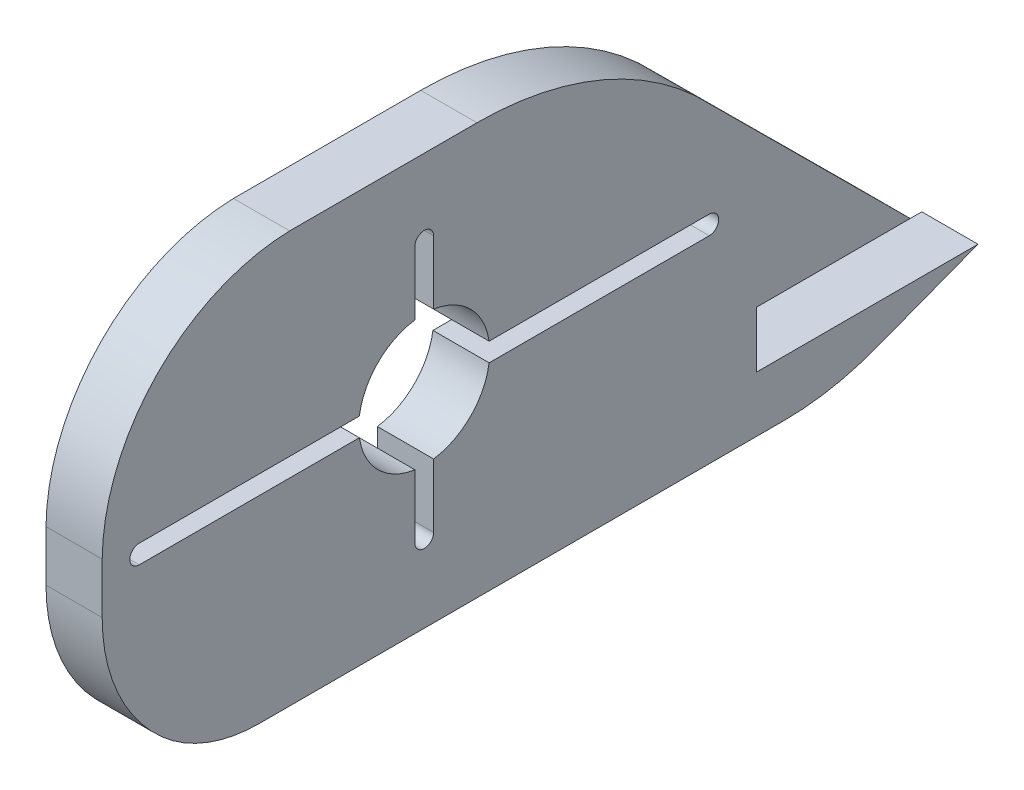
SolidWorks part; units mm, degrees
ref_plane "Front Plane" through (0, 0, 0) normal (0, 0, 1) x (1, 0, 0)
ref_plane "Top Plane" through (0, 0, 0) normal (0, 1, 0) x (1, 0, 0)
ref_plane "Right Plane" through (0, 0, 0) normal (1, 0, 0) x (0, 0, -1)
sketch "Sketch1" plane through (0, 0, 0) normal (0, 1, 0) x (1, 0, 0)
  line L8 (-9.9025, 36.4566) -> (-20.3157, 23.2959) construction
  line L10 (0, 0) -> (0, -15.9475) construction
  line L12 (-9.9025, 36.4566) -> (-20.3157, 23.2959)
  line L15 (-20.9631, 21.4344) -> (-20.9631, -5.9026) construction
  line L16 (-19.4729, -6.2109) -> (-9.8452, -11.8182)
  line L19 (-9.8452, -11.8182) -> (-9.8452, -21.8182)
  line L22 (-9.8452, -21.8182) -> (-6.8452, -21.8182)
  line L23 (-6.8452, -21.8182) -> (-6.8452, -12.4305)
  line L24 (-6.8452, -12.4305) -> (6.8452, -12.4305)
  line L25 (-4.1595, 37.5951) -> (-7.5499, 37.5951)
  line L26 (4.1595, 37.5951) -> (1.3957, 42.8144)
  line L27 (1.3957, 42.8144) -> (0, 43.4367)
  line L28 (24.762, -2.7815) -> (19.4729, -6.2109)
  line L29 (26.1299, 14.9044) -> (26.1299, -0.2643)
  line L30 (18.8536, 25.1438) -> (25.4825, 16.7659)
  line L31 (-18.8536, 25.1438) -> (-25.4825, 16.7659)
  line L32 (-26.1299, 14.9044) -> (-26.1299, -0.2643)
  line L33 (-24.762, -2.7815) -> (-19.4729, -6.2109)
  line L34 (4.1595, 37.5951) -> (7.5499, 37.5951)
  line L35 (6.8452, -21.8182) -> (6.8452, -12.4305)
  line L36 (9.8452, -21.8182) -> (6.8452, -21.8182)
  line L37 (9.8452, -11.8182) -> (9.8452, -21.8182)
  line L38 (19.4729, -6.2109) -> (9.8452, -11.8182)
  line L39 (0, 0) -> (0, 47.8638) construction
  line L40 (-1.3957, 42.8144) -> (0, 43.4367)
  line L41 (-4.1595, 37.5951) -> (-1.3957, 42.8144)
  line L42 (9.9025, 36.4566) -> (20.3157, 23.2959)
  arc A1 (-7.5499, 37.5951) -> (-9.9025, 36.4566) centre (-7.5499, 34.5951) ccw construction
  circle A4 centre (-5.0017, 34.5359) radius 1.5 construction
  circle A8 centre (-5.0017, 34.5359) radius 1.5
  arc A11 (-7.5499, 37.5951) -> (-9.9025, 36.4566) centre (-7.5499, 34.5951) ccw
  arc A12 (-19.7137, -6.0547) -> (-19.4729, -6.2109) centre (-17.9631, -3.6185) ccw
  arc A14 (25.4825, 16.7659) -> (26.1299, 14.9044) centre (23.1299, 14.9044) cw
  arc A15 (26.1299, -0.2643) -> (24.762, -2.7815) centre (23.1299, -0.2643) cw
  arc A16 (19.7137, -6.0547) -> (19.4729, -6.2109) centre (17.9631, -3.6185) cw
  arc A17 (-26.1299, -0.2643) -> (-24.762, -2.7815) centre (-23.1299, -0.2643) ccw
  arc A18 (-25.4825, 16.7659) -> (-26.1299, 14.9044) centre (-23.1299, 14.9044) ccw
  arc A19 (7.5499, 37.5951) -> (9.9025, 36.4566) centre (7.5499, 34.5951) cw
  circle A20 centre (5.0017, 34.5359) radius 1.5
  point P28 (0.1548, -12.4305)
  point P33 (-20.9631, -5.343)
  point P37 (0, -12.4305)
  point P41 (0.1548, -12.4305)
  point P46 (26.1299, 15.9477)
  point P48 (26.1299, -1.8946)
  point P49 (-0.1548, -12.4305)
  point P50 (20.9631, -5.343)
  point P54 (-26.1299, -1.8946)
  point P57 (-26.1299, 15.9477)
  dimension "D1" = 3
  dimension "D3" = 3
  dimension "D4" = 10
extrude "Boss-Extrude2" add sketch "Sketch1" along normal blind 3 contours A11 L12 A12 L16 L19 L22 L23 A8 region at (0, 0, -10.7329)
mirror "Mirror1" about plane through (0, 0, 0) normal (1, 0, 0) of "Boss-Extrude2"
sketch "Sketch3" plane through (9.8452, 0, 0) normal (1, 0, 0) x (0, 0, -1)
  line L0 (0, 0) -> (-5.4214, -2.0662)
  line L1 (-10.362, -2.9757) -> (-38.362, -2.9757)
  line L2 (-46.7647, 6.1171) -> (-46.7647, 8.8248)
  line L3 (-36.7549, 18.9944) -> (-26.7549, 18.9944)
  line L4 (-14.3131, 13.6377) -> (-3.6185, 3)
  line L5 (-3.6185, 3) -> (0, 0)
  line L6 (-11.8182, 3) -> (-11.8182, 0) construction
  arc A0 (-5.4214, -2.0662) -> (-10.362, -2.9757) centre (-10.362, 10.8976) cw
  arc A1 (-38.362, -2.9757) -> (-43.5481, -1.0139) centre (-38.362, 4.8597) cw
  arc A2 (-43.5481, -1.0139) -> (-46.7647, 6.1171) centre (-37.2518, 6.1171) cw
  circle A5 centre (-29.5682, 8.0684) radius 5 construction
  arc A7 (-26.7549, 18.9944) -> (-14.3131, 13.6377) centre (-26.7549, 1.8671) cw
  arc A8 (-36.7549, 18.9944) -> (-46.7647, 8.8248) centre (-36.4897, 8.7223) ccw
  dimension "D1" = 10
  dimension "D2" = 17.75
  dimension "D3" = 28
  dimension "D4" = 10
extrude "Boss-Extrude3" add sketch "Sketch3" against normal blind 3
sketch "Sketch4" plane through (9.8452, 0, 0) normal (1, 0, 0) x (0, 0, -1)
  circle A0 centre (-29.5682, 8.0684) radius 5
mirror "Mirror2" about plane through (0, 0, 0) normal (1, 0, 0) of "Boss-Extrude3"
extrude "Cut-Extrude1" cut sketch "Sketch4" against normal up to surface (3 mm away) rebuild error yes
sketch "Sketch5" plane through (-9.8452, 0, 0) normal (-1, 0, 0) x (0, 0, 1)
  line L0 (14.3482, 8.0684) -> (44.7882, 8.0684) construction
  line L1 (14.3482, 8.5684) -> (44.7882, 8.5684)
  line L2 (14.3482, 7.5684) -> (44.7882, 7.5684)
  line L3 (29.5682, 1.2134) -> (29.5682, 14.9234) construction
  line L4 (29.0682, 1.2134) -> (29.0682, 14.9234)
  line L5 (30.0682, 1.2134) -> (30.0682, 14.9234)
  circle A0 centre (29.5682, 8.0684) radius 5 construction
  circle A1 centre (29.5682, 8.0684) radius 5 construction
  arc A2 (14.3482, 8.5684) -> (14.3482, 7.5684) centre (14.3482, 8.0684) ccw
  arc A3 (44.7882, 7.5684) -> (44.7882, 8.5684) centre (44.7882, 8.0684) ccw
  arc A4 (29.0682, 1.2134) -> (30.0682, 1.2134) centre (29.5682, 1.2134) ccw
  arc A5 (30.0682, 14.9234) -> (29.0682, 14.9234) centre (29.5682, 14.9234) ccw
  circle A6 centre (29.5682, 8.0684) radius 3.5
  point P5 (29.5682, 8.0684)
  point P11 (29.5682, 8.0684)
  dimension "D1" = 0.5
  dimension "D2" = 0.5
  dimension "D5" = 10
  dimension "D6" = 7
  dimension "D3" = 30.44
  dimension "D4" = 13.71
extrude "Cut-Extrude2" cut sketch "Sketch5" against normal blind 3 contours L5 A6 L2 | L2 A6 L4 | L4 A6 L1 | L1 A6 L5 | L2 A3 L1 A2 | L5 A4 L4 A5 region at (-9.8452, 9.7725, 27.8641) region at (-9.8452, 6.3644, 27.8641) region at (-9.8452, 9.7725, 31.2723) region at (-9.8452, 6.3644, 31.2723)
sketch "Sketch7" plane through (0, 3, 0) normal (0, 1, 0) x (1, 0, 0)
  line L0 (-14.4326, 22.0478) -> (3.5367, 8.507)
  line L1 (3.5367, 8.507) -> (-3.6851, -1.0766)
  line L2 (-3.6851, -1.0766) -> (-21.6544, 12.4642)
  line L3 (-21.6544, 12.4642) -> (-14.4326, 22.0478)
  line L26 (-6.8452, -3.6185) -> (-6.8452, -12.4305)
  line L27 (-6.8452, -3.6185) -> (-6.8452, -12.4305)
  line L42 (6.8452, -3.6185) -> (9.8452, -3.6185)
  line L43 (6.8452, -3.6185) -> (9.8452, -3.6185)
  line L44 (-9.9025, 36.4566) -> (-25.4825, 16.7659)
  line L45 (-9.9025, 36.4566) -> (-25.4825, 16.7659)
  line L46 (-19.4729, -6.2109) -> (-9.8452, -11.8182)
  line L47 (-19.4729, -6.2109) -> (-9.8452, -11.8182)
  line L48 (-9.8452, -11.8182) -> (-9.8452, -3.6185)
  line L50 (-9.8452, -11.8182) -> (-9.8452, -3.6185)
  line L52 (-24.762, -2.7815) -> (-19.4729, -6.2109)
  line L53 (-24.762, -2.7815) -> (-19.4729, -6.2109)
  line L54 (-9.8452, -3.6185) -> (-6.8452, -3.6185)
  line L55 (-9.8452, -3.6185) -> (-6.8452, -3.6185)
  line L56 (-26.1299, 14.9044) -> (-26.1299, -0.2643)
  line L57 (-26.1299, 14.9044) -> (-26.1299, -0.2643)
  line L58 (0, 43.4367) -> (-1.3957, 42.8144)
  line L59 (0, 43.4367) -> (-1.3957, 42.8144)
  line L60 (-1.3957, 42.8144) -> (-4.1595, 37.5951)
  line L61 (-1.3957, 42.8144) -> (-4.1595, 37.5951)
  line L62 (-4.1595, 37.5951) -> (-7.5499, 37.5951)
  line L64 (-4.1595, 37.5951) -> (-7.5499, 37.5951)
  line L66 (-6.8452, -12.4305) -> (6.8452, -12.4305)
  line L68 (-6.8452, -12.4305) -> (6.8452, -12.4305)
  line L70 (6.8452, -12.4305) -> (6.8452, -3.6185)
  line L72 (6.8452, -12.4305) -> (6.8452, -3.6185)
  line L74 (9.8452, -3.6185) -> (9.8452, -11.8182)
  line L76 (9.8452, -3.6185) -> (9.8452, -11.8182)
  line L78 (9.8452, -11.8182) -> (19.4729, -6.2109)
  line L80 (9.8452, -11.8182) -> (19.4729, -6.2109)
  line L82 (19.4729, -6.2109) -> (24.762, -2.7815)
  line L83 (19.4729, -6.2109) -> (24.762, -2.7815)
  line L84 (26.1299, -0.2643) -> (26.1299, 14.9044)
  line L85 (26.1299, -0.2643) -> (26.1299, 14.9044)
  line L86 (25.4825, 16.7659) -> (9.9025, 36.4566)
  line L87 (25.4825, 16.7659) -> (9.9025, 36.4566)
  line L88 (7.5499, 37.5951) -> (4.1595, 37.5951)
  line L89 (7.5499, 37.5951) -> (4.1595, 37.5951)
  line L90 (4.1595, 37.5951) -> (1.3957, 42.8144)
  line L91 (4.1595, 37.5951) -> (1.3957, 42.8144)
  line L92 (1.3957, 42.8144) -> (0, 43.4367)
  line L93 (1.3957, 42.8144) -> (0, 43.4367)
  circle A0 centre (-20.1199, 18.8207) radius 1
  circle A1 centre (2.0023, 2.1505) radius 1
  arc A3 (-7.5499, 37.5951) -> (-9.9025, 36.4566) centre (-7.5499, 34.5951) ccw
  arc A18 (-7.5499, 37.5951) -> (-9.9025, 36.4566) centre (-7.5499, 34.5951) ccw
  arc A19 (-25.4825, 16.7659) -> (-26.1299, 14.9044) centre (-23.1299, 14.9044) ccw
  arc A20 (-25.4825, 16.7659) -> (-26.1299, 14.9044) centre (-23.1299, 14.9044) ccw
  arc A22 (-26.1299, -0.2643) -> (-24.762, -2.7815) centre (-23.1299, -0.2643) ccw
  arc A24 (-26.1299, -0.2643) -> (-24.762, -2.7815) centre (-23.1299, -0.2643) ccw
  arc A25 (24.762, -2.7815) -> (26.1299, -0.2643) centre (23.1299, -0.2643) ccw
  arc A26 (24.762, -2.7815) -> (26.1299, -0.2643) centre (23.1299, -0.2643) ccw
  arc A27 (26.1299, 14.9044) -> (25.4825, 16.7659) centre (23.1299, 14.9044) ccw
  arc A28 (26.1299, 14.9044) -> (25.4825, 16.7659) centre (23.1299, 14.9044) ccw
  arc A29 (9.9025, 36.4566) -> (7.5499, 37.5951) centre (7.5499, 34.5951) ccw
  arc A30 (9.9025, 36.4566) -> (7.5499, 37.5951) centre (7.5499, 34.5951) ccw
  dimension "D2" = 12
  dimension "D3" = 22.5
  dimension "D1" = 0
sketch "Sketch8" plane through (0, 3, 0) normal (0, 1, 0) x (1, 0, 0)
  line L0 (-14.4326, 22.0478) -> (3.5367, 8.507) construction
  line L1 (3.5367, 8.507) -> (-3.6851, -1.0766) construction
  line L2 (-3.6851, -1.0766) -> (-21.6544, 12.4642) construction
  line L3 (-21.6544, 12.4642) -> (-14.4326, 22.0478) construction
  line L4 (-14.4326, 22.0478) -> (3.5367, 8.507)
  line L5 (3.5367, 8.507) -> (-3.6851, -1.0766)
  line L6 (-3.6851, -1.0766) -> (-21.6544, 12.4642)
  line L7 (-21.6544, 12.4642) -> (-14.4326, 22.0478)
  line L28 (-24.762, -2.7815) -> (-19.4729, -6.2109)
  line L30 (-6.8452, -3.6185) -> (-6.8452, -12.4305)
  line L31 (-6.8452, -3.6185) -> (-6.8452, -12.4305)
  line L44 (-24.762, -2.7815) -> (-19.4729, -6.2109)
  line L48 (6.8452, -3.6185) -> (9.8452, -3.6185)
  line L49 (6.8452, -3.6185) -> (9.8452, -3.6185)
  line L50 (-9.9025, 36.4566) -> (-25.4825, 16.7659)
  line L51 (-9.9025, 36.4566) -> (-25.4825, 16.7659)
  line L52 (-26.1299, 14.9044) -> (-26.1299, -0.2643)
  line L53 (-26.1299, 14.9044) -> (-26.1299, -0.2643)
  line L54 (-19.4729, -6.2109) -> (-9.8452, -11.8182)
  line L55 (-19.4729, -6.2109) -> (-9.8452, -11.8182)
  line L56 (-9.8452, -11.8182) -> (-9.8452, -3.6185)
  line L57 (-9.8452, -11.8182) -> (-9.8452, -3.6185)
  line L58 (-9.8452, -3.6185) -> (-6.8452, -3.6185)
  line L59 (-9.8452, -3.6185) -> (-6.8452, -3.6185)
  line L60 (0, 43.4367) -> (-1.3957, 42.8144)
  line L61 (0, 43.4367) -> (-1.3957, 42.8144)
  line L62 (-1.3957, 42.8144) -> (-4.1595, 37.5951)
  line L63 (-1.3957, 42.8144) -> (-4.1595, 37.5951)
  line L64 (-4.1595, 37.5951) -> (-7.5499, 37.5951)
  line L66 (-4.1595, 37.5951) -> (-7.5499, 37.5951)
  line L68 (-6.8452, -12.4305) -> (6.8452, -12.4305)
  line L70 (-6.8452, -12.4305) -> (6.8452, -12.4305)
  line L72 (6.8452, -12.4305) -> (6.8452, -3.6185)
  line L74 (6.8452, -12.4305) -> (6.8452, -3.6185)
  line L76 (9.8452, -3.6185) -> (9.8452, -11.8182)
  line L78 (9.8452, -3.6185) -> (9.8452, -11.8182)
  line L80 (9.8452, -11.8182) -> (19.4729, -6.2109)
  line L82 (9.8452, -11.8182) -> (19.4729, -6.2109)
  line L84 (19.4729, -6.2109) -> (24.762, -2.7815)
  line L85 (19.4729, -6.2109) -> (24.762, -2.7815)
  line L86 (26.1299, -0.2643) -> (26.1299, 14.9044)
  line L87 (26.1299, -0.2643) -> (26.1299, 14.9044)
  line L88 (25.4825, 16.7659) -> (9.9025, 36.4566)
  line L89 (25.4825, 16.7659) -> (9.9025, 36.4566)
  line L90 (7.5499, 37.5951) -> (4.1595, 37.5951)
  line L91 (7.5499, 37.5951) -> (4.1595, 37.5951)
  line L92 (4.1595, 37.5951) -> (1.3957, 42.8144)
  line L93 (4.1595, 37.5951) -> (1.3957, 42.8144)
  line L94 (1.3957, 42.8144) -> (0, 43.4367)
  line L95 (1.3957, 42.8144) -> (0, 43.4367)
  circle A0 centre (-20.1199, 18.8207) radius 1 construction
  circle A1 centre (2.0023, 2.1505) radius 1 construction
  circle A2 centre (-20.1199, 18.8207) radius 1
  circle A3 centre (2.0023, 2.1505) radius 1
  arc A5 (-7.5499, 37.5951) -> (-9.9025, 36.4566) centre (-7.5499, 34.5951) ccw
  arc A18 (-7.5499, 37.5951) -> (-9.9025, 36.4566) centre (-7.5499, 34.5951) ccw
  arc A19 (-25.4825, 16.7659) -> (-26.1299, 14.9044) centre (-23.1299, 14.9044) ccw
  arc A20 (-25.4825, 16.7659) -> (-26.1299, 14.9044) centre (-23.1299, 14.9044) ccw
  arc A21 (-26.1299, -0.2643) -> (-24.762, -2.7815) centre (-23.1299, -0.2643) ccw
  arc A22 (-26.1299, -0.2643) -> (-24.762, -2.7815) centre (-23.1299, -0.2643) ccw
  arc A23 (24.762, -2.7815) -> (26.1299, -0.2643) centre (23.1299, -0.2643) ccw
  arc A24 (24.762, -2.7815) -> (26.1299, -0.2643) centre (23.1299, -0.2643) ccw
  arc A25 (26.1299, 14.9044) -> (25.4825, 16.7659) centre (23.1299, 14.9044) ccw
  arc A26 (26.1299, 14.9044) -> (25.4825, 16.7659) centre (23.1299, 14.9044) ccw
  arc A27 (9.9025, 36.4566) -> (7.5499, 37.5951) centre (7.5499, 34.5951) ccw
  arc A28 (9.9025, 36.4566) -> (7.5499, 37.5951) centre (7.5499, 34.5951) ccw
  dimension "D1" = 0
sketch "Sketch9" plane through (0, 3, 0) normal (0, 1, 0) x (1, 0, 0)
  line L0 (3.5367, 8.507) -> (-3.6851, -1.0766) construction
  line L1 (-14.4326, 22.0478) -> (3.5367, 8.507) construction
  line L2 (-3.6851, -1.0766) -> (-21.6544, 12.4642) construction
  line L3 (-21.6544, 12.4642) -> (-14.4326, 22.0478) construction
  line L4 (3.5367, 8.507) -> (-3.6851, -1.0766)
  line L5 (-14.4326, 22.0478) -> (3.5367, 8.507)
  line L6 (-3.6851, -1.0766) -> (-21.6544, 12.4642)
  line L7 (-21.6544, 12.4642) -> (-14.4326, 22.0478)
  line L28 (-24.762, -2.7815) -> (-19.4729, -6.2109)
  line L30 (-6.8452, -3.6185) -> (-6.8452, -12.4305)
  line L31 (-6.8452, -3.6185) -> (-6.8452, -12.4305)
  line L44 (-24.762, -2.7815) -> (-19.4729, -6.2109)
  line L48 (6.8452, -3.6185) -> (9.8452, -3.6185)
  line L49 (6.8452, -3.6185) -> (9.8452, -3.6185)
  line L50 (-9.9025, 36.4566) -> (-25.4825, 16.7659)
  line L51 (-26.1299, 14.9044) -> (-26.1299, -0.2643)
  line L52 (-19.4729, -6.2109) -> (-9.8452, -11.8182)
  line L53 (-19.4729, -6.2109) -> (-9.8452, -11.8182)
  line L54 (-9.8452, -11.8182) -> (-9.8452, -3.6185)
  line L55 (-9.8452, -11.8182) -> (-9.8452, -3.6185)
  line L56 (-9.8452, -3.6185) -> (-6.8452, -3.6185)
  line L57 (-9.8452, -3.6185) -> (-6.8452, -3.6185)
  line L58 (0, 43.4367) -> (-1.3957, 42.8144)
  line L59 (0, 43.4367) -> (-1.3957, 42.8144)
  line L60 (-1.3957, 42.8144) -> (-4.1595, 37.5951)
  line L61 (-1.3957, 42.8144) -> (-4.1595, 37.5951)
  line L62 (-4.1595, 37.5951) -> (-7.5499, 37.5951)
  line L63 (-4.1595, 37.5951) -> (-7.5499, 37.5951)
  line L64 (-6.8452, -12.4305) -> (6.8452, -12.4305)
  line L65 (-6.8452, -12.4305) -> (6.8452, -12.4305)
  line L66 (6.8452, -12.4305) -> (6.8452, -3.6185)
  line L67 (6.8452, -12.4305) -> (6.8452, -3.6185)
  line L68 (9.8452, -3.6185) -> (9.8452, -11.8182)
  line L69 (9.8452, -3.6185) -> (9.8452, -11.8182)
  line L70 (9.8452, -11.8182) -> (19.4729, -6.2109)
  line L71 (9.8452, -11.8182) -> (19.4729, -6.2109)
  line L72 (19.4729, -6.2109) -> (24.762, -2.7815)
  line L73 (19.4729, -6.2109) -> (24.762, -2.7815)
  line L74 (26.1299, -0.2643) -> (26.1299, 14.9044)
  line L75 (26.1299, -0.2643) -> (26.1299, 14.9044)
  line L76 (25.4825, 16.7659) -> (9.9025, 36.4566)
  line L77 (25.4825, 16.7659) -> (9.9025, 36.4566)
  line L78 (7.5499, 37.5951) -> (4.1595, 37.5951)
  line L79 (7.5499, 37.5951) -> (4.1595, 37.5951)
  line L80 (4.1595, 37.5951) -> (1.3957, 42.8144)
  line L81 (4.1595, 37.5951) -> (1.3957, 42.8144)
  line L82 (1.3957, 42.8144) -> (0, 43.4367)
  line L83 (1.3957, 42.8144) -> (0, 43.4367)
  circle A0 centre (2.0023, 2.1505) radius 1 construction
  circle A1 centre (-20.1199, 18.8207) radius 1 construction
  circle A2 centre (2.0023, 2.1505) radius 1
  circle A4 centre (-20.1199, 18.8207) radius 1
  arc A6 (-7.5499, 37.5951) -> (-9.9025, 36.4566) centre (-7.5499, 34.5951) ccw
  arc A21 (-7.5499, 37.5951) -> (-9.9025, 36.4566) centre (-7.5499, 34.5951) ccw
  arc A22 (-25.4825, 16.7659) -> (-26.1299, 14.9044) centre (-23.1299, 14.9044) ccw
  arc A23 (-26.1299, -0.2643) -> (-24.762, -2.7815) centre (-23.1299, -0.2643) ccw
  arc A24 (-26.1299, -0.2643) -> (-24.762, -2.7815) centre (-23.1299, -0.2643) ccw
  arc A25 (24.762, -2.7815) -> (26.1299, -0.2643) centre (23.1299, -0.2643) ccw
  arc A26 (24.762, -2.7815) -> (26.1299, -0.2643) centre (23.1299, -0.2643) ccw
  arc A27 (26.1299, 14.9044) -> (25.4825, 16.7659) centre (23.1299, 14.9044) ccw
  arc A28 (26.1299, 14.9044) -> (25.4825, 16.7659) centre (23.1299, 14.9044) ccw
  arc A29 (9.9025, 36.4566) -> (7.5499, 37.5951) centre (7.5499, 34.5951) ccw
  arc A30 (9.9025, 36.4566) -> (7.5499, 37.5951) centre (7.5499, 34.5951) ccw
  dimension "D1" = 0
sketch "Sketch10" plane through (0, 3, 0) normal (0, 1, 0) x (1, 0, 0)
  line L16 (-6.8452, -3.6185) -> (-6.8452, -12.4305)
  line L17 (-6.8452, -12.4305) -> (6.8452, -12.4305)
  line L18 (6.8452, -12.4305) -> (6.8452, -3.6185)
  line L19 (6.8452, -3.6185) -> (9.8452, -3.6185)
  line L20 (9.8452, -3.6185) -> (9.8452, -11.8182)
  line L21 (9.8452, -11.8182) -> (19.4729, -6.2109)
  line L22 (19.4729, -6.2109) -> (24.762, -2.7815)
  line L23 (26.1299, -0.2643) -> (26.1299, 14.9044)
  line L24 (25.4825, 16.7659) -> (9.9025, 36.4566)
  line L25 (7.5499, 37.5951) -> (-7.5499, 37.5951)
  line L26 (-9.9025, 36.4566) -> (-25.4825, 16.7659)
  line L27 (-26.1299, 14.9044) -> (-26.1299, -0.2643)
  line L28 (-24.762, -2.7815) -> (-19.4729, -6.2109)
  line L29 (-19.4729, -6.2109) -> (-9.8452, -11.8182)
  line L30 (-9.8452, -11.8182) -> (-9.8452, -3.6185)
  line L31 (-9.8452, -3.6185) -> (-6.8452, -3.6185)
  line L32 (-6.8452, -3.6185) -> (-6.8452, -12.4305)
  line L33 (-6.8452, -12.4305) -> (6.8452, -12.4305)
  line L34 (6.8452, -12.4305) -> (6.8452, -3.6185)
  line L35 (6.8452, -3.6185) -> (9.8452, -3.6185)
  line L36 (9.8452, -3.6185) -> (9.8452, -11.8182)
  line L37 (9.8452, -11.8182) -> (19.4729, -6.2109)
  line L38 (19.4729, -6.2109) -> (24.762, -2.7815)
  line L39 (26.1299, -0.2643) -> (26.1299, 14.9044)
  line L40 (25.4825, 16.7659) -> (9.9025, 36.4566)
  line L41 (7.5499, 37.5951) -> (-7.5499, 37.5951)
  line L42 (-9.9025, 36.4566) -> (-25.4825, 16.7659)
  line L43 (-26.1299, 14.9044) -> (-26.1299, -0.2643)
  line L44 (-24.762, -2.7815) -> (-19.4729, -6.2109)
  line L45 (-19.4729, -6.2109) -> (-9.8452, -11.8182)
  line L46 (-9.8452, -11.8182) -> (-9.8452, -3.6185)
  line L47 (-9.8452, -3.6185) -> (-6.8452, -3.6185)
  arc A6 (24.762, -2.7815) -> (26.1299, -0.2643) centre (23.1299, -0.2643) ccw
  arc A7 (26.1299, 14.9044) -> (25.4825, 16.7659) centre (23.1299, 14.9044) ccw
  arc A8 (9.9025, 36.4566) -> (7.5499, 37.5951) centre (7.5499, 34.5951) ccw
  arc A9 (-7.5499, 37.5951) -> (-9.9025, 36.4566) centre (-7.5499, 34.5951) ccw
  arc A10 (-25.4825, 16.7659) -> (-26.1299, 14.9044) centre (-23.1299, 14.9044) ccw
  arc A11 (-26.1299, -0.2643) -> (-24.762, -2.7815) centre (-23.1299, -0.2643) ccw
  arc A12 (24.762, -2.7815) -> (26.1299, -0.2643) centre (23.1299, -0.2643) ccw
  arc A13 (26.1299, 14.9044) -> (25.4825, 16.7659) centre (23.1299, 14.9044) ccw
  arc A14 (9.9025, 36.4566) -> (7.5499, 37.5951) centre (7.5499, 34.5951) ccw
  arc A15 (-7.5499, 37.5951) -> (-9.9025, 36.4566) centre (-7.5499, 34.5951) ccw
  arc A16 (-25.4825, 16.7659) -> (-26.1299, 14.9044) centre (-23.1299, 14.9044) ccw
  arc A17 (-26.1299, -0.2643) -> (-24.762, -2.7815) centre (-23.1299, -0.2643) ccw
  dimension "D1" = 0
extrude "Cut-Extrude3" cut sketch "Sketch9" against normal blind 10 contours L7 L6 L4 L5 | A4 | A2 region at (-9.0588, 3, -10.4856) region at (2.0023, 3, -2.1505) region at (-20.1199, 3, -18.8207)
sketch "Sketch16" plane through (0, 3, 0) normal (0, 1, 0) x (1, 0, 0)
  circle A0 centre (13.2517, 13.6459) radius 1.5
  circle A1 centre (5.0017, 34.5359) radius 1.5 construction
  dimension "D1" = 3
  dimension "D2" = 20.89
  dimension "D3" = 8.25
extrude "Cut-Extrude4" cut sketch "Sketch16" against normal blind 10
sketch "Sketch18" plane through (6.8452, 0, 0) normal (-1, 0, 0) x (0, 0, 1)
  circle A0 centre (29.5682, 8.0684) radius 3.5
  dimension "D1" = 7
sketch "Sketch19" plane through (0, 3, 0) normal (0, 1, 0) x (1, 0, 0)
  circle A0 centre (0, -2.643) radius 1.5
  dimension "D1" = 3
extrude "Cut-Extrude6" cut sketch "Sketch19" against normal blind 10
extrude "Boss-Extrude4" add sketch "Sketch18" against normal blind 20
sketch "Sketch20" plane through (26.8452, 0, 0) normal (1, 0, 0) x (0, 0, -1)
  circle A0 centre (-29.5682, 8.0684) radius 1.5
  dimension "D1" = 3
extrude "Cut-Extrude7" cut sketch "Sketch20" against normal blind 12
sketch "Sketch21" plane through (-9.8452, 0, 0) normal (-1, 0, 0) x (0, 0, 1)
  line L1 (11.8182, 3) -> (-46.6791, 3)
  line L2 (11.8182, 3) -> (11.8182, 0)
  line L3 (11.8182, 0) -> (-46.6791, 0)
  line L4 (-46.6791, 3) -> (-46.6791, 0)
extrude "Cut-Extrude8" cut sketch "Sketch21" against normal through all both and the other way through all
sketch "Sketch22" plane through (0, 3, 0) normal (0, 1, 0) x (1, 0, 0)
  line L0 (6.8452, -11.8182) -> (-6.8452, -11.8182) construction
  line L1 (-6.8452, -11.8182) -> (6.8452, -11.8182)
  line L2 (-6.8452, -11.8182) -> (-6.8452, -13.6506)
  line L3 (-6.8452, -13.6506) -> (6.8452, -13.6506)
  line L4 (6.8452, -11.8182) -> (6.8452, -13.6506)
  line L5 (-6.8452, -3.6185) -> (-6.8452, -14.3131) construction
extrude "Cut-Extrude9" cut sketch "Sketch22" against normal through all both
sketch "Sketch23" plane through (26.8452, 0, 0) normal (1, 0, 0) x (0, 0, -1)
  circle A0 centre (-29.5682, 8.0684) radius 3.5
  dimension "D1" = 7
extrude "Cut-Extrude10" cut sketch "Sketch23" against normal up to surface (20 mm away) up to face at (6.8452, 5.0611, 22.9774)
sketch "Sketch24" plane through (0, 18.9944, 0) normal (0, 1, 0) x (1, 0, 0)
  line L1 (5.0769, 2.4254) -> (17.0171, 2.4254)
  line L2 (5.0769, 2.4254) -> (5.0769, -57.6516)
  line L3 (5.0769, -57.6516) -> (17.0171, -57.6516)
  line L4 (17.0171, 2.4254) -> (17.0171, -57.6516)
extrude "Cut-Extrude11" cut sketch "Sketch24" against normal through all both and the other way through all
